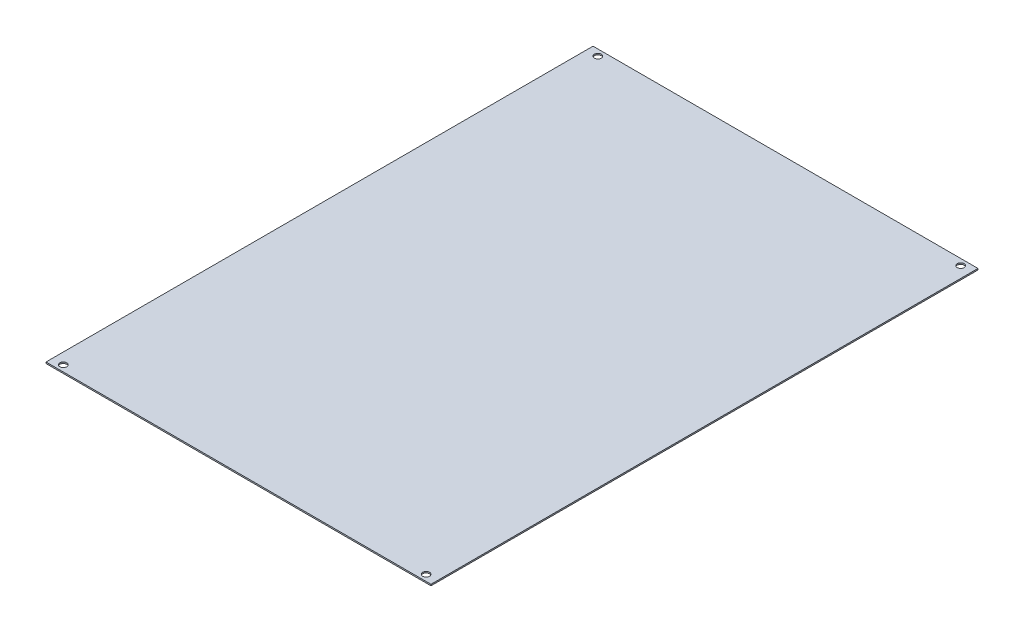
SolidWorks part; units mm, degrees
note: The reader was unsure of these and kept them because the rebuilt part matched: thickness of "Base-Flange1", "Sheet-Metal1", "Sheet-Metal2".
ref_plane "Front Plane" through (0, 0, 0) normal (0, 0, 1) x (1, 0, 0)
ref_plane "Top Plane" through (0, 0, 0) normal (0, 1, 0) x (1, 0, 0)
ref_plane "Right Plane" through (0, 0, 0) normal (1, 0, 0) x (0, 0, -1)
sketch "Sketch1" plane through (0, 0, 0) normal (0, 1, 0) x (1, 0, 0)
  line L1 (139, -197.5) -> (-139, -197.5)
  line L2 (139, -197.5) -> (139, 197.5)
  line L3 (139, 197.5) -> (-139, 197.5)
  line L4 (-139, -197.5) -> (-139, 197.5)
  line L5 (139, -197.5) -> (-139, 197.5) construction
  line L6 (139, 197.5) -> (-139, -197.5) construction
  point P1 (0, 0)
  dimension "D1" = 278
  dimension "D2" = 395
base flange "Base-Flange1" sketch "Sketch1" thickness 1 reverse thickness direction no parameters "D1"=0.7366
sketch "Sketch6" plane through (0, 0, 0) normal (0, 1, 0) x (1, 0, 0)
  line L0 (139, 197.5) -> (-139, 197.5) construction
  line L1 (-139, 197.5) -> (-139, -197.5) construction
  line L2 (139, -197.5) -> (139, 197.5) construction
  line L3 (-139, -197.5) -> (139, -197.5) construction
  circle A0 centre (-131, 193) radius 2.5
  circle A1 centre (131, 193) radius 2.5
  circle A2 centre (131, -193) radius 2.5
  circle A3 centre (-131, -193) radius 2.5
  dimension "D1" = 5
  dimension "D2" = 4.5
  dimension "D3" = 8
  dimension "D4" = 8
  dimension "D5" = 4.5
  dimension "D6" = 4.5
  dimension "D7" = 8
  dimension "D8" = 4.5
  dimension "D9" = 8
extrude "Screw" cut sketch "Sketch6" against normal through all normal cut yes
sketch "Bend-Lines1" [suppressed] plane through (0, 0, 0) normal (0, 1, 0) x (1, 0, 0)
sketch "Bounding-Box1" [suppressed] plane through (0, 0, 0) normal (0, 1, 0) x (1, 0, 0)
sheet metal parameters "Sheet-Metal1" thickness 1 parameters "D1"=0.7366, "D7"=2
flat pattern "Flat-Pattern1" [suppressed]
sketch "Bend-Lines2" plane through (0, 0, 0) normal (0, 1, 0) x (1, 0, 0)
sketch3d "Bounding-Box2" [suppressed]
  line L0 (-139, 196.5, 0) -> (-139, -196.5, 0) construction
  line L1 (139, 196.5, 0) -> (139, -196.5, 0) construction
  line L2 (-139, 196.5, 0) -> (139, 196.5, 0) construction
  line L3 (-139, -196.5, 0) -> (139, -196.5, 0) construction
sheet metal parameters "Sheet-Metal2" thickness 1 parameters "D1"=0.7366, "D7"=2
flat pattern "Flat-Pattern1"
sketch "Bend-Lines2" plane through (0, 0, 0) normal (0, 1, 0) x (1, 0, 0)
sketch3d "Bounding-Box2" [suppressed]
  line L0 (-139, 197.5, 0) -> (-139, -197.5, 0) construction
  line L1 (139, 197.5, 0) -> (139, -197.5, 0) construction
  line L2 (-139, 197.5, 0) -> (139, 197.5, 0) construction
  line L3 (-139, -197.5, 0) -> (139, -197.5, 0) construction
equation "\"top_lid_length\"=298"
equation "\"top_lid_width\"=395"
equation "\"D2@Sketch1\"= \"top_lid_width\""
